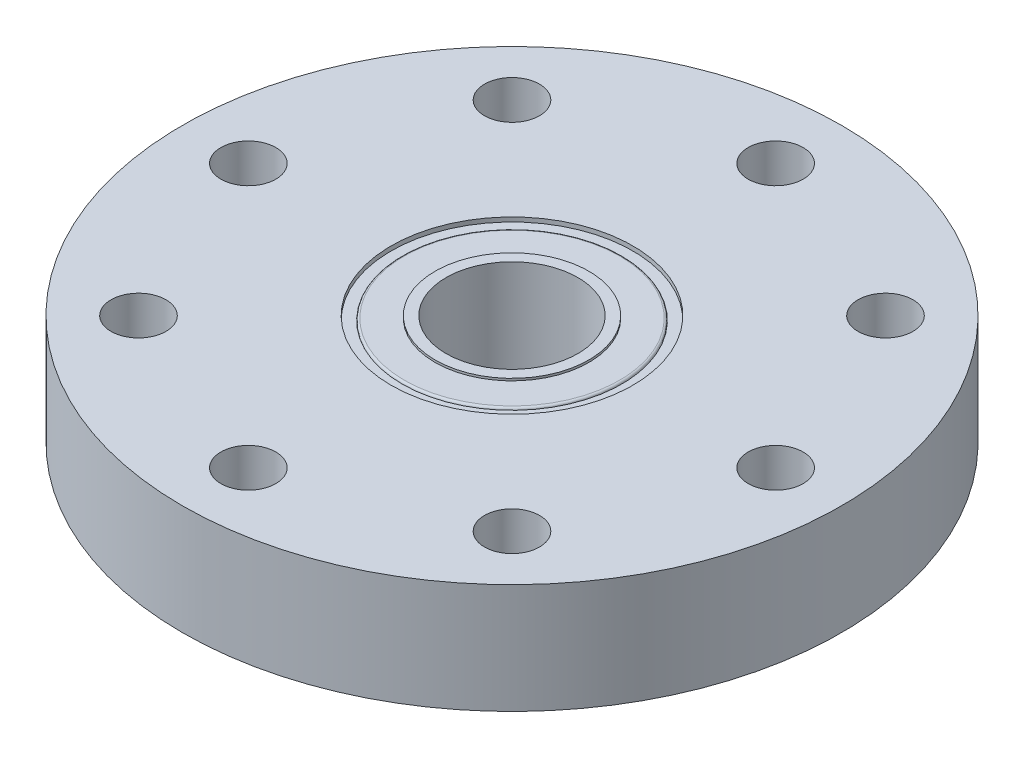
SolidWorks part; units mm, degrees
ref_plane "Front Plane" through (0, 0, 0) normal (0, 0, 1) x (1, 0, 0)
ref_plane "Top Plane" through (0, 0, 0) normal (0, 1, 0) x (1, 0, 0)
ref_plane "Right Plane" through (0, 0, 0) normal (1, 0, 0) x (0, 0, -1)
sketch "Sketch1" plane through (0, 0, 0) normal (0, 1, 0) x (1, 0, 0)
  line L0 (0, 12) -> (0, -12) construction
  line L1 (-12, 0) -> (12, 0) construction
  line L6 (8.5, 8.5) -> (-8.5, 8.5) construction
  circle A0 centre (0, 0) radius 15
  circle A2 centre (0, 12) radius 1.25
  circle A3 centre (0, -12) radius 1.25
  circle A4 centre (0, 0) radius 3
  circle A5 centre (-12, 0) radius 1.25
  circle A6 centre (12, 0) radius 1.25
  circle A7 centre (8.5, 8.5) radius 1.25
  circle A8 centre (8.5, -8.5) radius 1.25
  circle A9 centre (-8.5, -8.5) radius 1.25
  circle A10 centre (-8.5, 8.5) radius 1.25
  point P6 (0, 0)
  point P12 (0, 0)
  point P20 (0, 8.5)
  dimension "D1" = 4
extrude "Boss-Extrude1" add sketch "Sketch1" along normal blind 5
sketch "Sketch4" plane through (0, 5, 0) normal (0, 1, 0) x (1, 0, 0)
  line L0 (0, 5) -> (0, 5.5) construction
  line L1 (0, -3) -> (0, -3.5) construction
  circle A0 centre (0, 0) radius 5
  circle A1 centre (0, 0) radius 5.5
  circle A2 centre (0, 0) radius 3.5
  circle A3 centre (0, 0) radius 3 construction
extrude "Cut-Extrude1" cut sketch "Sketch4" against normal blind 0.2 contours A1 A0 region at (-5.3444, 5, 0)
extrude "Cut-Extrude2" cut sketch "Sketch4<3>" against normal blind 0.1 contours A0 A2 region at (-4.8586, 5, 0)
sketch "Sketch4<3>" plane through (0, 5, 0) normal (0, 1, 0) x (1, 0, 0) same geometry as "Sketch4"
sketch "Sketch5" plane through (0, 0, 0) normal (0, -1, 0) x (1, 0, 0)
  circle A0 centre (0, 0) radius 3.5
  circle A2 centre (0, 0) radius 5
  circle A3 centre (0, 0) radius 5.75
extrude "Cut-Extrude3" cut sketch "Sketch5" against normal blind 0.1 contours A2 A0 region at (-4.8586, 0, 0)
extrude "Cut-Extrude4" cut sketch "Sketch5<3>" against normal blind 0.2 contours A3 A2 region at (-5.5874, 0, 0)
sketch "Sketch5<3>" plane through (0, 0, 0) normal (0, -1, 0) x (1, 0, 0) same geometry as "Sketch5"
fillet "Fillet1" radius 0.1 2 edges at (0, 4.9, 5) (0, 0.1, -5)
